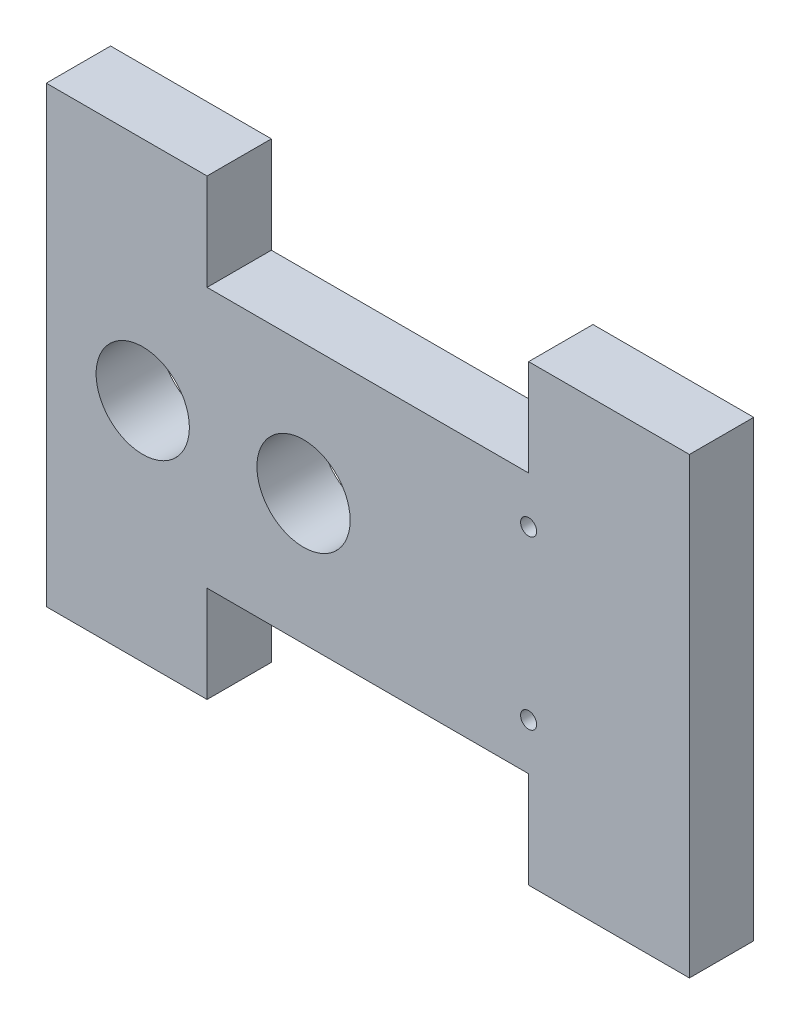
SolidWorks part; units mm, degrees
ref_plane "Front Plane" through (0, 0, 0) normal (0, 0, 1) x (1, 0, 0)
ref_plane "Top Plane" through (0, 0, 0) normal (0, 1, 0) x (1, 0, 0)
ref_plane "Right Plane" through (0, 0, 0) normal (1, 0, 0) x (0, 0, -1)
sketch "Sketch1" plane through (0, 0, 0) normal (0, 0, 1) x (1, 0, 0)
  line L0 (-93.3491, 17.1926) -> (-83.3491, 17.1926)
  line L1 (-98.3491, 20.1926) -> (-98.3491, 6.0926)
  line L2 (-78.3491, 20.1926) -> (-78.3491, 6.0926)
  line L3 (-93.3491, 9.0926) -> (-83.3491, 9.0926)
  line L5 (-78.3491, 6.0926) -> (-83.3491, 6.0926)
  line L6 (-83.3491, 6.0926) -> (-83.3491, 9.0926)
  line L8 (-98.3491, 6.0926) -> (-93.3491, 6.0926)
  line L9 (-93.3491, 6.0926) -> (-93.3491, 9.0926)
  line L11 (-98.3491, 20.1926) -> (-93.3491, 20.1926)
  line L12 (-93.3491, 20.1926) -> (-93.3491, 17.1926)
  line L14 (-78.3491, 20.1926) -> (-83.3491, 20.1926)
  line L15 (-83.3491, 20.1926) -> (-83.3491, 17.1926)
extrude "Boss-Extrude1" add sketch "Sketch1" along normal blind 1.7
extrude "Boss-Extrude4" add sketch "Sketch1<4>" against normal blind 0.3
sketch "Sketch1<4>" plane through (0, 0, 0) normal (0, 0, 1) x (1, 0, 0) same geometry as "Sketch1"
sketch "Sketch6" plane through (0, 0, 1.7) normal (0, 0, 1) x (1, 0, 0)
  circle A0 centre (-95.3491, 13.1426) radius 1.45
extrude "Cut-Extrude1" cut sketch "Sketch6" against normal blind 2
sketch "Sketch7" plane through (0, 0, 1.7) normal (0, 0, 1) x (1, 0, 0)
  circle A0 centre (-90.3491, 13.1426) radius 1.45
extrude "Cut-Extrude2" cut sketch "Sketch7" against normal blind 2
sketch "Sketch8" plane through (0, 0, 1.7) normal (0, 0, 1) x (1, 0, 0)
  circle A0 centre (-83.3491, 15.7426) radius 0.25
extrude "Cut-Extrude3" cut sketch "Sketch8" against normal blind 2
sketch "Sketch9" plane through (0, 0, 1.7) normal (0, 0, 1) x (1, 0, 0)
  circle A0 centre (-83.3491, 10.5426) radius 0.25
extrude "Cut-Extrude4" cut sketch "Sketch9" against normal blind 2
